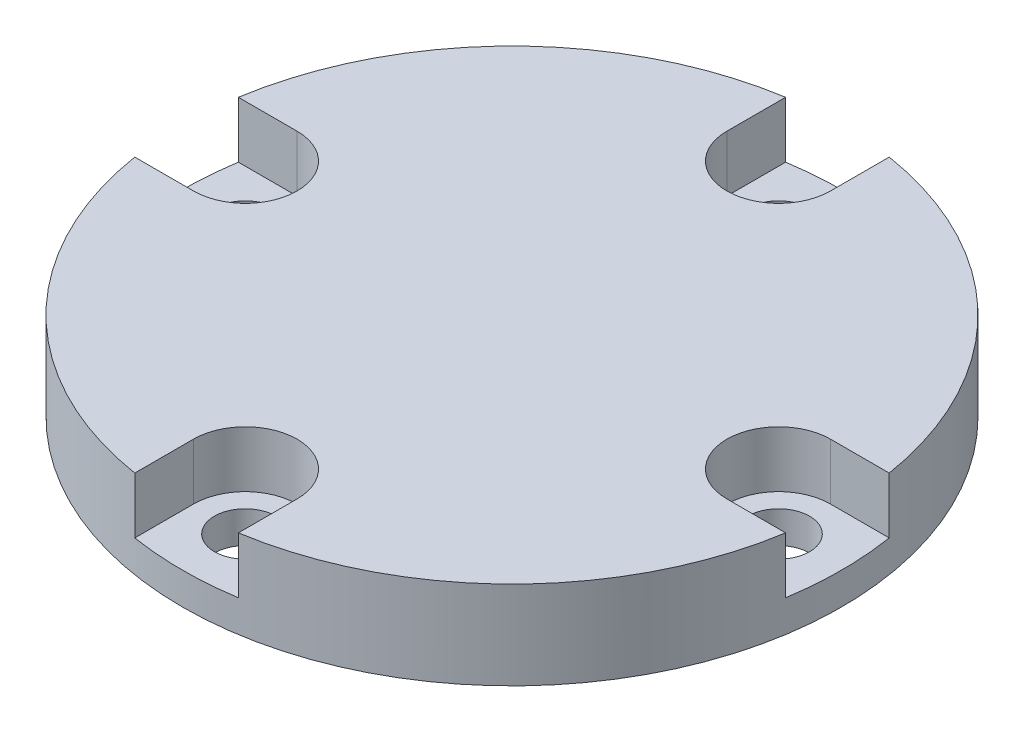
SolidWorks part; units mm, degrees
ref_plane "Front Plane" through (0, 0, 0) normal (0, 0, 1) x (1, 0, 0)
ref_plane "Top Plane" through (0, 0, 0) normal (0, 1, 0) x (1, 0, 0)
ref_plane "Right Plane" through (0, 0, 0) normal (1, 0, 0) x (0, 0, -1)
sketch "Sketch1" plane through (0, 0, 0) normal (0, 1, 0) x (1, 0, 0)
  circle A0 centre (0, 0) radius 14.95
  dimension "D1" = 29.9
extrude "Boss-Extrude1" add sketch "Sketch1" along normal blind 4
sketch "Sketch2" plane through (0, 4, 0) normal (0, 1, 0) x (1, 0, 0)
  line L0 (-2.35, 12.1) -> (-2.35, 14.7641)
  line L1 (2.35, 12.1) -> (2.35, 14.7641)
  line L2 (12.1, -2.35) -> (14.7641, -2.35)
  line L3 (12.1, 2.35) -> (14.7641, 2.35)
  line L4 (-2.35, -12.1) -> (-2.35, -14.7641)
  line L5 (2.35, -12.1) -> (2.35, -14.7641)
  line L6 (-12.1, 2.35) -> (-14.7641, 2.35)
  line L7 (-12.1, -2.35) -> (-14.7641, -2.35)
  circle A0 centre (0, 0) radius 12.1 construction
  arc A1 (-2.35, 12.1) -> (2.35, 12.1) centre (0, 12.1) ccw
  circle A2 centre (0, 0) radius 14.95 construction
  arc A3 (-2.35, 14.7641) -> (2.35, 14.7641) centre (0, 0) cw
  arc A4 (12.1, 2.35) -> (12.1, -2.35) centre (12.1, 0) ccw
  arc A5 (14.7641, 2.35) -> (14.7641, -2.35) centre (0, 0) cw
  arc A6 (2.35, -12.1) -> (-2.35, -12.1) centre (0, -12.1) ccw
  arc A7 (2.35, -14.7641) -> (-2.35, -14.7641) centre (0, 0) cw
  arc A8 (-12.1, -2.35) -> (-12.1, 2.35) centre (-12.1, 0) ccw
  arc A9 (-14.7641, -2.35) -> (-14.7641, 2.35) centre (0, 0) cw
  point P29 (0, 0)
  dimension "D1" = 24.2
  dimension "D2" = 4.7
  dimension "D3" = 4
extrude "Cut-Extrude1" cut sketch "Sketch2" against normal blind 2.55
sketch "Sketch3" plane through (0, 1.45, 0) normal (0, 1, 0) x (1, 0, 0)
  circle A0 centre (0, 12.1) radius 1.4
  circle A1 centre (-12.1, 0) radius 1.4
  circle A2 centre (0, -12.1) radius 1.4
  circle A3 centre (12.1, 0) radius 1.4
  dimension "D1" = 2.8
extrude "Cut-Extrude2" cut sketch "Sketch3" against normal blind 2.55
